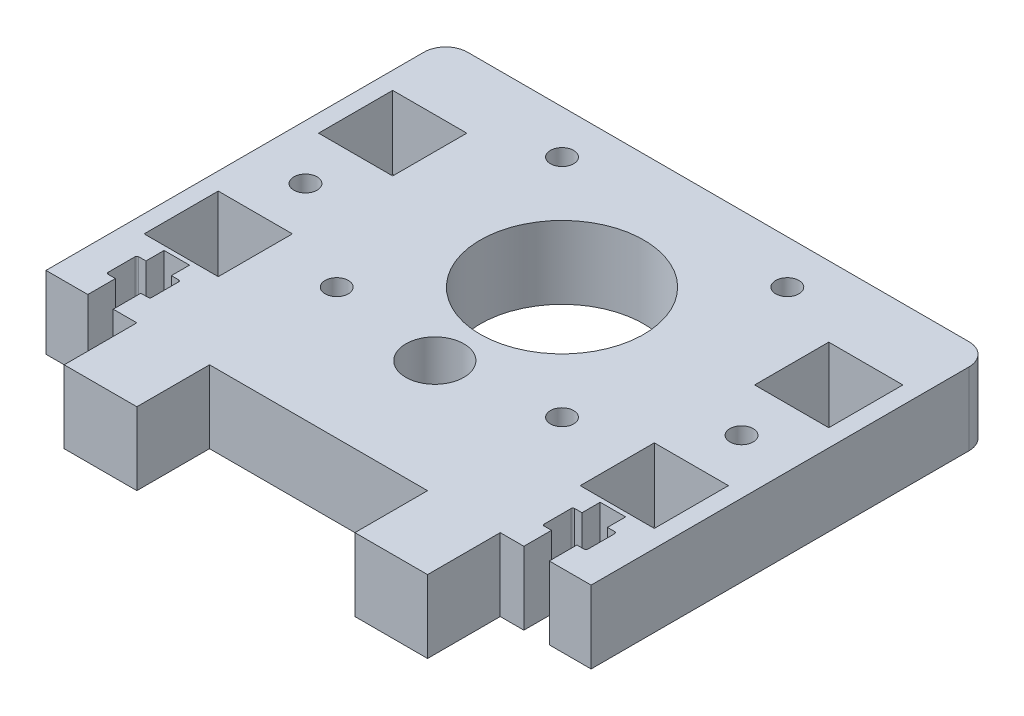
SolidWorks part; units mm, degrees
ref_plane "Front Plane" through (0, 0, 0) normal (0, 0, 1) x (1, 0, 0)
ref_plane "Top Plane" through (0, 0, 0) normal (0, 1, 0) x (1, 0, 0)
ref_plane "Right Plane" through (0, 0, 0) normal (1, 0, 0) x (0, 0, -1)
sketch "Sketch1" plane through (0, 0, 0) normal (0, 1, 0) x (1, 0, 0)
  line L0 (0, 29) -> (0, -6) construction
  line L1 (-34.5, 29) -> (0, 29)
  line L2 (-37.5, 26) -> (-37.5, -26)
  line L3 (-37.5, -26) -> (-25, -26)
  line L4 (0, 29) -> (0, 18.75)
  line L5 (0, -3.75) -> (0, -6)
  line L6 (0, -14) -> (0, -26) construction
  line L7 (-11.25, 7.5) -> (0, 7.5) construction
  line L8 (0, -14) -> (0, -26)
  line L9 (-30, 19.3) -> (-30, 9.1) construction
  line L10 (-37.5, 2.2) -> (0, 2.2) construction
  line L11 (-35.1, 19.3) -> (-24.9, 19.3)
  line L12 (-35.1, 19.3) -> (-35.1, 9.1)
  line L13 (-35.1, 9.1) -> (-24.9, 9.1)
  line L14 (-24.9, 19.3) -> (-24.9, 9.1)
  line L15 (-35.1, 19.3) -> (-24.9, 9.1) construction
  line L16 (-35.1, 9.1) -> (-24.9, 19.3) construction
  line L17 (-35.1, -4.7) -> (-24.9, -14.9) construction
  line L18 (-35.1, -14.9) -> (-24.9, -4.7) construction
  line L19 (-24.9, -14.9) -> (-24.9, -4.7)
  line L20 (-35.1, -4.7) -> (-24.9, -4.7)
  line L21 (-35.1, -14.9) -> (-35.1, -4.7)
  line L22 (-35.1, -14.9) -> (-24.9, -14.9)
  line L23 (-30, -4.7) -> (-30, -14.9) construction
  line L24 (-30, -9.8) -> (-30, 14.2) construction
  line L25 (0, 7.5) -> (-15.5, 23) construction
  line L35 (-15, -26) -> (0, -26)
  line L43 (-20, -36) -> (-20, -26.9) construction
  line L44 (-15, -26) -> (-15, -36)
  line L45 (-15, -36) -> (-25, -36)
  line L46 (-25, -36) -> (-25, -26)
  arc A1 (-34.5, 29) -> (-37.5, 26) centre (-34.5, 26) ccw
  arc A2 (0, 18.75) -> (0, -3.75) centre (0, 7.5) ccw
  circle A4 centre (-15.5, 23) radius 1.6
  circle A6 centre (-15.5, -8) radius 1.6
  circle A7 centre (-30, 2.2) radius 1.6
  arc A10 (0, -6) -> (0, -14) centre (0, -10) ccw
  point P0 (0, 0)
  point P28 (-30, 14.2)
  point P39 (-30, -9.8)
  dimension "D7" = 22.5
  dimension "D17" = 8
  dimension "D14" = 3.2
  dimension "D6" = 3
  dimension "D19" = 3.2
  dimension "D1" = 55
  dimension "D9" = 10.2
  dimension "D10" = 10.2
  dimension "D22" = 10
  dimension "D23" = 10
  dimension "D16" = 17.5
  dimension "D11" = 24
  dimension "D13" = 2.2
  dimension "D3" = 37.5
  dimension "D4" = 31
  dimension "D5" = 15.5
  dimension "D15" = 26
  dimension "D18" = 37.5
  dimension "D20" = 20
  dimension "D8" = 16
  dimension "D12" = 30
extrude "MainLayout" add sketch "Sketch1" along normal blind 10
sketch "Sketch2" plane through (0, 10, 0) normal (0, 1, 0) x (1, 0, 0)
  line L0 (-30, -26) -> (-30, -15.5) construction
  line L1 (-28.25, -22.2) -> (-28.25, -26)
  line L2 (-37.5, -26) -> (-25, -26) construction
  line L3 (-28.25, -15.5) -> (-31.75, -15.5)
  line L4 (-31.75, -15.5) -> (-31.75, -18)
  line L5 (-31.75, -18) -> (-32.75, -18)
  line L6 (-33, -18.25) -> (-33, -21.95)
  line L7 (-32.75, -22.2) -> (-31.75, -22.2)
  line L8 (-31.75, -22.2) -> (-31.75, -26)
  line L9 (-31.75, -26) -> (-28.25, -26)
  line L10 (-27.25, -22.2) -> (-28.25, -22.2)
  line L11 (-27, -18.25) -> (-27, -21.95)
  line L12 (-28.25, -18) -> (-27.25, -18)
  line L13 (-28.25, -15.5) -> (-28.25, -18)
  line L14 (0, -26) -> (0, -14) construction
  line L30 (-30, -26) -> (-30, -15.5) construction
  arc A0 (-27, -18.25) -> (-27.25, -18) centre (-27.25, -18.25) ccw
  arc A1 (-32.75, -18) -> (-33, -18.25) centre (-32.75, -18.25) ccw
  arc A2 (-27.25, -22.2) -> (-27, -21.95) centre (-27.25, -21.95) ccw
  arc A3 (-33, -21.95) -> (-32.75, -22.2) centre (-32.75, -21.95) ccw
  point P17 (0, -20)
  point P38 (-27, -18)
  point P41 (-33, -18)
  point P44 (-27, -22.2)
  point P47 (-33, -22.2)
  dimension "D8" = 0.25
  dimension "D1" = 1.75
  dimension "D2" = 0
  dimension "D3" = 4.2
  dimension "D5" = 10.5
  dimension "D6" = 3
  dimension "D4" = 8
  dimension "D7" = 30
extrude "TSlot" cut sketch "Sketch2" against normal through all
mirror "Mirror1" about plane through (0, 0, 0) normal (1, 0, 0) of "TSlot", "MainLayout"
equation "\"Y-ROD-SPACING\"=75"
equation "\"Y-BED-OFFSET\"=2"
equation "\"Y-BED-ROD-INSET\"=3.5"
equation "\"T-SLOT-NUT-FILLET-RADIUS\"=0.25"
equation "\"T-SLOT-SCREW-SHAFT-RADIUS\"=1.75"
equation "\"T-SLOT-SCREW-SHAFT-CUTOUT-LENGTH\"=10.5"
equation "\"T-SLOT-NUT-DEPTH\"=4.2"
equation "\"T-SLOT-NUT-WIDTH\"=3"
equation "\"T-SLOT-NUT-END-DISTANCE\"=8"
equation "\"ACRYLIC-TAB-CUTOUT-SIZE\"=\"ACRYLIC-THICKNESS\"+\"ACRYLIC-TAB-TOLERANCE\"*2"
equation "\"ACRYLIC-TAB-WIDTH\"=\"ACRYLIC-THICKNESS\""
equation "\"ACRYLIC-M3-HOLE\"=3.2"
equation "\"SMOOTHROD-CAP-SCREW-DISTANCE\"=20"
equation "\"FRAME-WIDTH-INNER\"=370"
equation "\"NEMA17-HOLE-SPACING\"=31"
equation "\"NEMA17-CENTRAL-CUTOUT\"=22.5"
equation "\"D7@Sketch1\"=\"NEMA17-CENTRAL-CUTOUT\""
equation "\"D5@Sketch1\"=\"NEMA17-HOLE-SPACING\"/2"
equation "\"D4@Sketch1\"=\"NEMA17-HOLE-SPACING\""
equation "\"D19@Sketch1\"=\"ACRYLIC-M3-HOLE\""
equation "\"D14@Sketch1\"=\"ACRYLIC-M3-HOLE\""
equation "\"D9@Sketch1\"=\"ACRYLIC-TAB-CUTOUT-SIZE\""
equation "\"D10@Sketch1\"=\"ACRYLIC-TAB-CUTOUT-SIZE\""
equation "\"D23@Sketch1\"=\"ACRYLIC-TAB-WIDTH\""
equation "\"D22@Sketch1\"=\"ACRYLIC-TAB-WIDTH\""
equation "\"D5@Sketch2\"=\"T-SLOT-SCREW-SHAFT-CUTOUT-LENGTH\""
equation "\"D4@Sketch2\"=\"T-SLOT-NUT-END-DISTANCE\""
equation "\"D3@Sketch2\"=\"T-SLOT-NUT-DEPTH\""
equation "\"D1@Sketch2\"=\"T-SLOT-SCREW-SHAFT-RADIUS\""
equation "\"D8@Sketch2\"=\"T-SLOT-NUT-FILLET-RADIUS\""
equation "\"Z-BRACKET-REACH\"=55"
equation "\"D1@Sketch1\"=\"Z-BRACKET-REACH\""
equation "\"Z-ROD-SPACING\"=17.5"
equation "\"ACRYLIC-THICKNESS\"=10"
equation "\"TOP-BRACKET-SPACING\"=40"
equation "\"SMOOTHROD-X-LENGTH\"=350"
equation "\"SMOOTHROD-Y-LENGTH\"=350"
equation "\"SMOOTHROD-Z-LENGTH\"=350"
equation "\"SMOOTHROD-TIGHTENING-HEADROOM\"=1"
equation "\"LEADSCREW-Z-LENGTH\"=300"
equation "\"D16@Sketch1\"=\"Z-ROD-SPACING\""
equation "\"X-ROD-SPACING\"=45"
equation "\"ACRYLIC-THICKNESS2\"=4.5"
equation "\"SCREW-LENGTH-FRAME\"=\"ACRYLIC-THICKNESS\" + 10"
equation "\"SCREW-HEAD-RADIUS\"=6"
equation "\"PRINTED-X-SMOOTHROD-DIAMETER\"=8.2"
equation "\"PRINTED-X-SMOOTHROD-CUTOUT\"=10"
equation "\"PRINTED-X-BASE-HEIGHT\"=10"
equation "\"PRINTED-LM8UU-CUTOUT-SIZE\"=16"
equation "\"PRINTED-LM8UU-CUTOUT-LENGTH\"=24.5"
equation "\"PRINTED-X-IDLER-HEIGHT\"=16"
equation "\"PSU-MOUNTING-WIDTH\"=95"
equation "\"PSU-MOUNTING-HEIGHT\"=177"
equation "\"D1@MainLayout\"=\"ACRYLIC-THICKNESS\""
equation "\"Z-ROD-INSET\"=16"
equation "\"Y-BELT-TO-ROD-DISTANCE\"=20"
equation "\"SPOOL-HOLDER-ROD-SPACING\"=150"
equation "\"D8@Sketch1\"=\"Z-ROD-INSET\""
equation "\"Y-BED-SCREW-SPACING\"=209"
equation "\"Y-BED-SCREW-CUTOUT-SLOT-HEIGHT\"=1"
equation "\"ACRYLIC-TAB-TOLERANCE\"=.1"
equation "\"SCREW-LENGTH-MOTOR\"=\"ACRYLIC-THICKNESS\" + 5"
equation "\"SCREW-LENGTH-EXTRUDER\"=28"
equation "\"ACRYLIC-X-CARRIAGE-WIDTH\"=55"
equation "\"ACRYLIC-X-CARRIAGE-HEIGHT\"=75"
equation "\"ACRYLIC-X-CARRIAGE-LM8UU-CUTOUT-WIDTH\"=24.25"
equation "\"ACRYLIC-X-CARRIAGE-SCREW-SPACING-X\"=15"
equation "\"ACRYLIC-X-CARRIAGE-SCREW-SPACING-Y\"=33"
equation "\"ACRYLIC-X-CARRIAGE-CENTER-TAB-SPACING\"=14"
equation "\"ACRYLIC-X-CARRIAGE-EXTRUDER-OFFSET\"=26"
equation "\"ACRYLIC-X-CARRIAGE-EXTRUDER-ANGLE\"=90"
equation "\"ACRYLIC-X-CARRIAGE-EXTRUDER-SHELF-DEPTH\"=\"ACRYLIC-X-CARRIAGE-EXTRUDER-OFFSET\" + 30"
equation "\"ACRYLIC-X-CARRIAGE-EXTRUDER-BRACE-SPACING\"=23"
equation "\"ACRYLIC-X-CARRIAGE-EXTRUDER-BRACE-TAB-OFFSET\"=20"
equation "\"ACRYLIC-X-CARRIAGE-EXTRUDER-BRACE-HEIGHT\"=35"
equation "\"ACRYLIC-X-CARRIAGE-EXTRUDER-BRACE-SCREW-SPACING\"=22"
